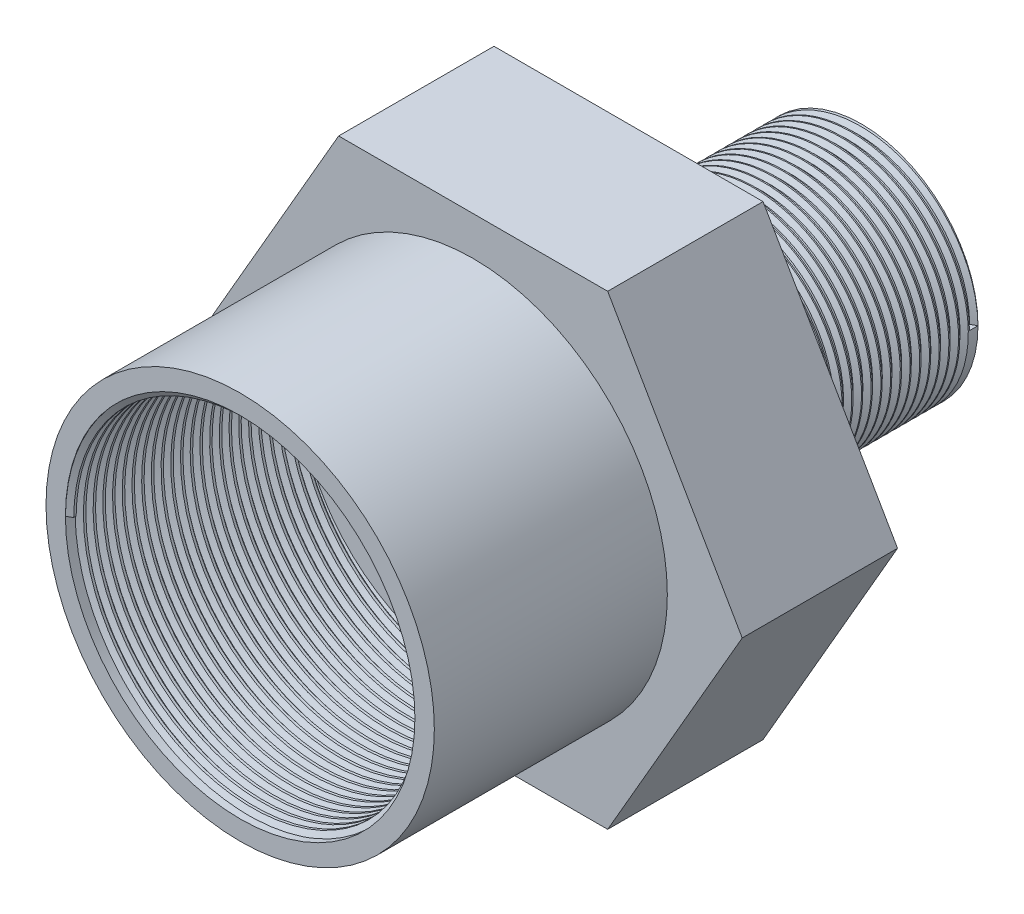
SolidWorks part; units mm, degrees
ref_plane "Front Plane" through (0, 0, 0) normal (0, 0, 1) x (1, 0, 0)
ref_plane "Top Plane" through (0, 0, 0) normal (0, 1, 0) x (1, 0, 0)
ref_plane "Right Plane" through (0, 0, 0) normal (1, 0, 0) x (0, 0, -1)
sketch "Sketch1" plane through (0, 0, 0) normal (0, 0, 1) x (1, 0, 0)
  line L1 (34.641, 0) -> (17.3205, 30)
  line L2 (17.3205, 30) -> (-17.3205, 30)
  line L3 (-17.3205, 30) -> (-34.641, 0)
  line L4 (-34.641, 0) -> (-17.3205, -30)
  line L5 (-17.3205, -30) -> (17.3205, -30)
  line L6 (17.3205, -30) -> (34.641, 0)
  circle A1 centre (0, 0) radius 30 construction
  dimension "D1" = 60
extrude "Boss-Extrude1" add sketch "Sketch1" along normal blind 20
sketch "Sketch2" plane through (0, 0, 20) normal (0, 0, 1) x (1, 0, 0)
  circle A0 centre (0, 0) radius 25
  circle A1 centre (0, 0) radius 22.5
  dimension "D1" = 50
  dimension "D2" = 45
extrude "Boss-Extrude2" add sketch "Sketch2" along normal blind 30
sketch "Sketch3" plane through (0, 0, 0) normal (0, 0, -1) x (-1, 0, 0)
  circle A0 centre (0, 0) radius 15
  circle A1 centre (0, 0) radius 12.5
  dimension "D1" = 30
  dimension "D2" = 25
extrude "Boss-Extrude3" add sketch "Sketch3" along normal blind 30
thread "Thread1" pitch 1.25 method extrude profile "Thread Profile1" start angle 0, offset 0, length 0, pitch 1.25, diameter 45
ref_plane "Plane1" through (-22.5, 0, 50) normal (0, -1, 0) x (-1, 0, 0)
sketch "Thread Profile1" plane through (-22.5, 0, 50) normal (0, -1, 0) x (-1, 0, 0)
  line L0 (0, 0) -> (0, 1.25) construction
  line L11 (0, 0) -> (0, 1.0937)
  line L12 (0, 1.0937) -> (-0.6766, 0.7031)
  line L13 (-0.6766, 0.7031) -> (-0.6766, 0.3906)
  line L15 (-0.6766, 0.3906) -> (0, 0)
  line L17 (-0.6766, 0.5469) -> (0, 0.5469) construction
  point P2 (0, 0)
  dimension "Pitch" = 1.25
  dimension "Profile_Angle" = 60
  dimension "Profile_Land" = 0.3125
  dimension "Profile_Height" = 0.6766
thread "Thread3" pitch 1.25 method cut profile "Thread Profile3" start angle 0, offset 0, length 0, pitch 1.25, diameter 30
ref_plane "Plane3" through (15, 0, -30) normal (0, -1, 0) x (1, 0, 0)
sketch "Thread Profile3" plane through (15, 0, -30) normal (0, -1, 0) x (1, 0, 0)
  line L0 (0, 0) -> (0, 1.25) construction
  line L11 (0, 0) -> (0, 1.0937)
  line L12 (0, 1.0937) -> (-0.6766, 0.7031)
  line L13 (-0.6766, 0.7031) -> (-0.6766, 0.3906)
  line L15 (-0.6766, 0.3906) -> (0, 0)
  line L17 (-0.6766, 0.5469) -> (0, 0.5469) construction
  point P2 (0, 0)
  dimension "Pitch" = 1.25
  dimension "Profile_Angle" = 60
  dimension "Profile_Land" = 0.3125
  dimension "Profile_Height" = 0.6766
